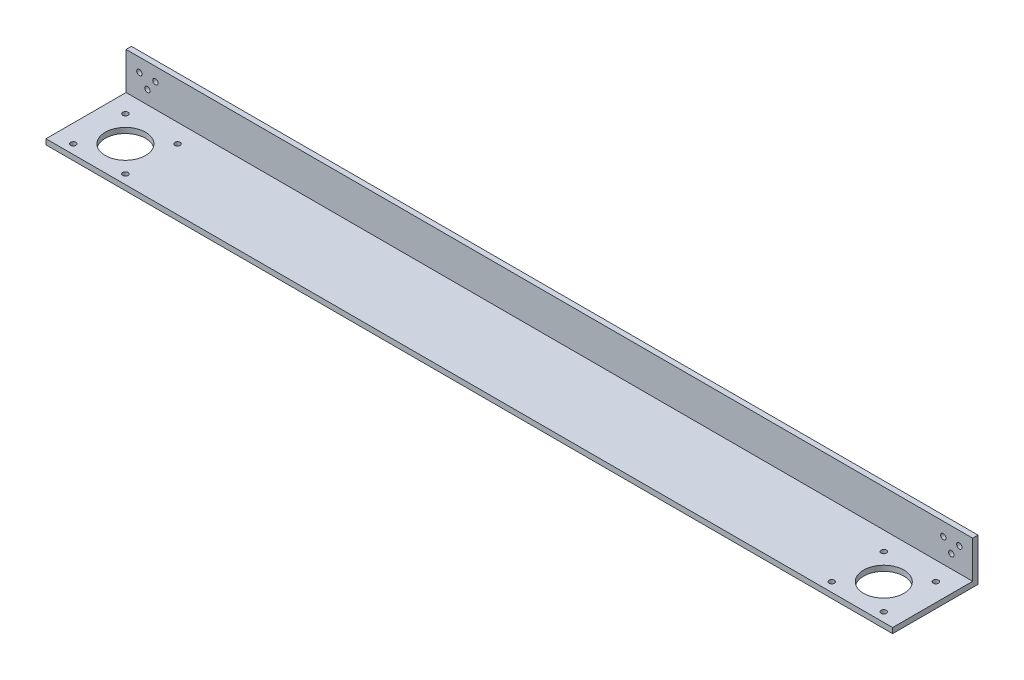
SolidWorks part; units mm, degrees
ref_plane "Front Plane" through (0, 0, 0) normal (0, 0, 1) x (1, 0, 0)
ref_plane "Top Plane" through (0, 0, 0) normal (0, 1, 0) x (1, 0, 0)
ref_plane "Right Plane" through (0, 0, 0) normal (1, 0, 0) x (0, 0, -1)
sketch "Sketch1" plane through (0, 0, 0) normal (1, 0, 0) x (0, 0, -1)
  line L0 (0, 0) -> (-50.8, 0)
  line L1 (-50.8, 0) -> (-50.8, 3.175)
  line L2 (-50.8, 3.175) -> (-3.175, 3.175)
  line L3 (-3.175, 3.175) -> (-3.175, 25.4)
  line L4 (-3.175, 25.4) -> (0, 25.4)
  line L5 (0, 25.4) -> (0, 0)
  dimension "LHeight" = 25.4
  dimension "LWidth" = 50.8
  dimension "LMaterialThickness" = 3.175
  dimension "D1" = 47.625
  dimension "D2" = 22.225
  dimension "D3" = 3.175
extrude "Boss-Extrude1" add sketch "Sketch1" along normal blind 503.65
sketch "TopHoles-Sketch2" plane through (0, 3.175, 0) normal (0, 1, 0) x (1, 0, 0)
  line L1 (503.65, -50.8) -> (0, -50.8) construction
  line L2 (0, -3.175) -> (0, -50.8) construction
  line L3 (503.65, -3.175) -> (503.65, -50.8) construction
  circle A0 centre (26.25, -29.8) radius 12
  circle A1 centre (477.4, -29.8) radius 12
  circle A2 centre (10.75, -14.3) radius 1.5875
  circle A3 centre (41.75, -14.3) radius 1.5875
  circle A4 centre (461.9, -14.3) radius 1.5875
  circle A5 centre (492.9, -14.3) radius 1.5875
  circle A6 centre (10.75, -45.3) radius 1.5875
  circle A7 centre (41.75, -45.3) radius 1.5875
  circle A8 centre (461.9, -45.3) radius 1.5875
  circle A9 centre (492.9, -45.3) radius 1.5875
  dimension "D9" = 3.175
  dimension "D10" = 24
  dimension "D3" = 31
  dimension "D4" = 15.5
  dimension "D5" = 15.5
  dimension "D6" = 31
  dimension "D7" = 15.5
  dimension "D13" = 26.25
  dimension "D8" = 31
  dimension "D11" = 26.25
  dimension "D2" = 5.5
extrude "TopHoles-Cut-Extrude1" cut sketch "TopHoles-Sketch2" against normal through all
sketch "BackSideHoles-Sketch3" plane through (0, 0, 0) normal (0, 0, -1) x (-1, 0, 0)
  line L1 (-503.65, 25.4) -> (0, 25.4) construction
  line L2 (0, 0) -> (0, 25.4) construction
  line L3 (-503.65, 0) -> (-503.65, 25.4) construction
  circle A0 centre (-495.7125, 17.4625) radius 1.5875
  circle A1 centre (-486.1875, 17.4625) radius 1.5875
  circle A3 centre (-490.95, 11.1125) radius 1.5875
  circle A4 centre (-12.7, 11.1125) radius 1.5875
  circle A6 centre (-17.4625, 17.4625) radius 1.5875
  circle A7 centre (-7.9375, 17.4625) radius 1.5875
  dimension "D7" = 3.175
  dimension "D4" = 11.1125
  dimension "D3" = 7.9375
  dimension "D1" = 7.9375
  dimension "D2" = 17.4625
  dimension "D6" = 17.4625
  dimension "D5" = 7.9375
  dimension "D8" = 12.7
  dimension "D9" = 12.7
extrude "BackSideHoles-Cut-Extrude2" cut sketch "BackSideHoles-Sketch3" against normal through all
equation "\"MidBackRailWidth\"= 2.00in"
equation "\"MidBackRailHeight\"= 1.00in"
equation "\"RailThickness\"= .125in'Spec"
equation "\"SideRailHoleY1FromEdge\"= \"HoleOffsetFromEdge\""
equation "\"SideRailHoleX1FromSide\"= \"HoleOffsetFromSide\""
equation "\"StepperHoleDiameter\"= 24mm"
equation "\"StepperMountingHoleDiameter\"= 3.175mm"
equation "\"StepperMountingHoleDistance\"= 31mm'Spec"
equation "\"VSWidth\"= 1.25in'Spec"
equation "\"StepperMountingHoleOffsetFromLeftRightEdge\"= \"StepperMountingHoleOffsetFromItsSide\""
equation "\"HoleOffsetFromEdge\"= \"RailThickness\" * 2.5"
equation "\"HoleOffsetFromSide\"= \"RailThickness\" * 3.5"
equation "\"StepperMountingHoleOffsetFromItsSide\"= 5.5mm'Spec"
equation "\"SideRailHoleX2FromSide\"= \"VSWidth\" - \"HoleOffsetFromEdge\" - \"RailThickness\"'Equals 20.6375"
equation "\"FasteningHoleDiameter\"= .125in"
equation "\"SideRailHoleY2FromSide\"= \"HoleOffsetFromSide\""
equation "\"FrontBackRailLength\"= 510mm"
equation "\"LHeight@Sketch1\"=\"MidBackRailHeight\""
equation "\"LWidth@Sketch1\"=\"MidBackRailWidth\""
equation "\"D3@TopHoles-Sketch2\" = \"StepperMountingHoleDistance\""
equation "\"D4@TopHoles-Sketch2\" = \"StepperMountingHoleDistance\" / 2"
equation "\"D5@TopHoles-Sketch2\" = \"StepperMountingHoleDistance\" / 2"
equation "\"D6@TopHoles-Sketch2\" = \"StepperMountingHoleDistance\""
equation "\"D7@TopHoles-Sketch2\" = \"StepperMountingHoleDistance\" / 2"
equation "\"D9@TopHoles-Sketch2\" = \"StepperMountingHoleDiameter\""
equation "\"D10@TopHoles-Sketch2\" = \"StepperHoleDiameter\""
equation "\"D4@BackSideHoles-Sketch3\" = \"SideRailHoleY2FromSide\""
equation "\"D7@BackSideHoles-Sketch3\" = \"FasteningHoleDiameter\""
equation "\"D1@Boss-Extrude1\"= \"MidBackRailLength\""
equation "\"D3@BackSideHoles-Sketch3\"=\"SideRailHoleY1FromEdge\""
equation "\"D1@BackSideHoles-Sketch3\"=\"SideRailHoleX1FromSide\" - \"RailThickness\""
equation "\"D2@BackSideHoles-Sketch3\"=\"SideRailHoleX2FromSide\" - \"RailThickness\""
equation "\"D6@BackSideHoles-Sketch3\"=\"SideRailHoleX2FromSide\" - \"RailThickness\""
equation "\"D5@BackSideHoles-Sketch3\"=\"SideRailHoleX1FromSide\" - \"RailThickness\""
equation "\"StepperHoleToAlignHorizontallyWithGantryBlock\"= \"LinearGBWithRailDepth\" + \"GABDistanceFromBackToFirstPulley\"'Equals 26.25"
equation "\"D13@TopHoles-Sketch2\"=\"StepperHoleToAlignHorizontallyWithGantryBlock\" "
equation "\"D8@TopHoles-Sketch2\"=\"StepperMountingHoleDistance\""
equation "\"D11@TopHoles-Sketch2\"=\"StepperHoleToAlignHorizontallyWithGantryBlock\" "
equation "\"LinearGBWithRailDepth\"= 12.75mm'Spec"
equation "\"GABDistanceFromBackToFirstPulley\"= 13.5mm"
equation "\"MidBackRailLength\"= \"FrontBackRailLength\" - \"RailThickness\" * 2'MidBackRail buts up against MidSideRail"
equation "\"VSMidSideRailHoleXFromSideToCenter\"= \"RailThickness\" * 6"
equation "\"D8@BackSideHoles-Sketch3\"=\"VSMidSideRailHoleXFromSideToCenter\"- \"RailThickness\" - \"RailThickness\""
equation "\"D9@BackSideHoles-Sketch3\"=\"VSMidSideRailHoleXFromSideToCenter\" - \"RailThickness\" - \"RailThickness\""
equation "\"D2@TopHoles-Sketch2\"=\"StepperMountingHoleOffsetFromLeftRightEdge\""
